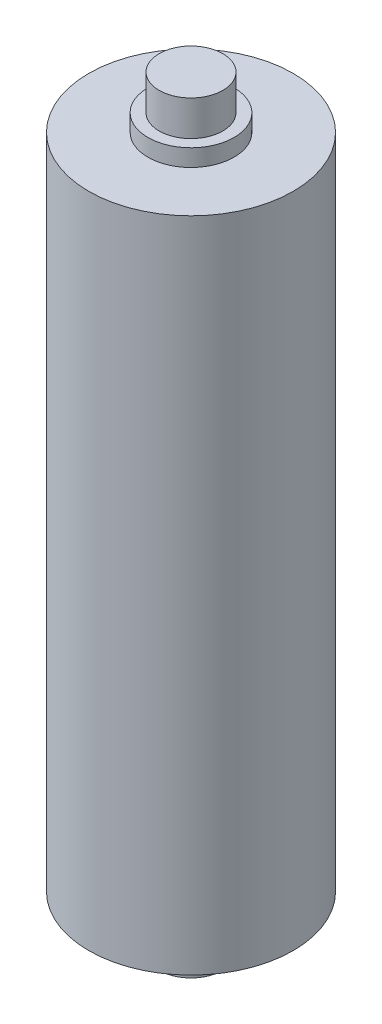
SolidWorks part; units mm, degrees
ref_plane "Front Plane" through (0, 0, 0) normal (0, 0, 1) x (1, 0, 0)
ref_plane "Top Plane" through (0, 0, 0) normal (0, 1, 0) x (1, 0, 0)
ref_plane "Right Plane" through (0, 0, 0) normal (1, 0, 0) x (0, 0, -1)
sketch "Sketch1" plane through (0, 0, 0) normal (0, 1, 0) x (1, 0, 0)
  circle A0 centre (0, 0) radius 6.425
  circle A1 centre (0, 0) radius 15.25
  circle A2 centre (0, 0) radius 4.75
  dimension "D1" = 12.85
  dimension "D2" = 30.5
  dimension "D3" = 9.5
extrude "Boss-Extrude1" add sketch "Sketch1" along normal mid plane 103.2 contours A0 A2 | A2 region at (-6.2433, 0, 0) region at (0, 0, 0)
extrude "Boss-Extrude2" add sketch "Sketch1<3>" along normal mid plane 113.7 contours A2 region at (0, 0, 0)
sketch "Sketch1<3>" plane through (0, 0, 0) normal (0, 1, 0) x (1, 0, 0) same geometry as "Sketch1"
extrude "Boss-Extrude4" add sketch "Sketch1<5>" along normal mid plane 98.1 contours A1 A0 region at (-14.8187, 0, 0)
sketch "Sketch1<5>" plane through (0, 0, 0) normal (0, 1, 0) x (1, 0, 0) same geometry as "Sketch1"
